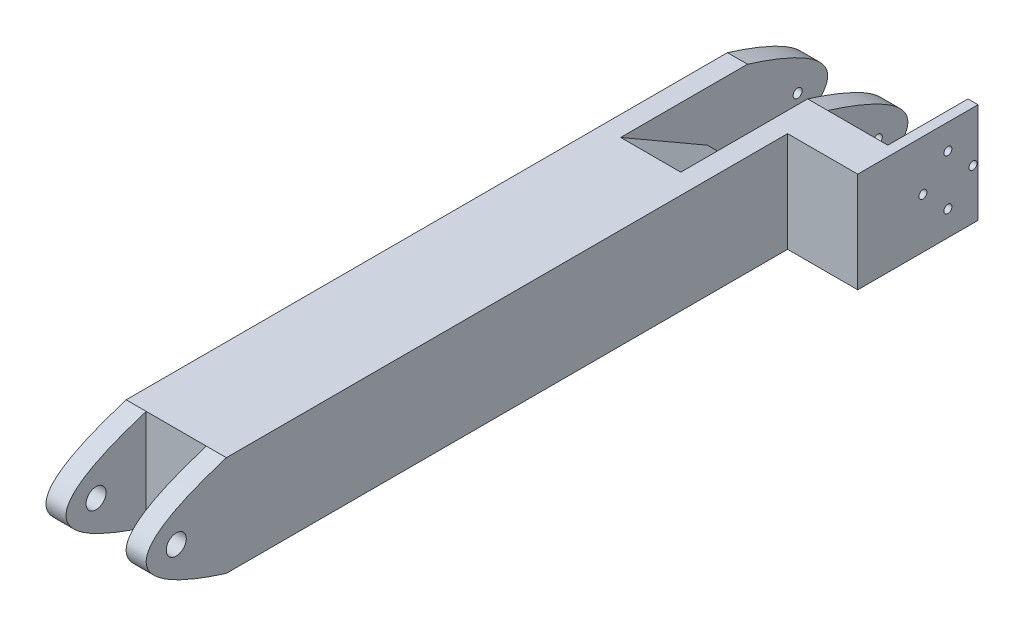
SolidWorks part; units mm, degrees
ref_plane "Front Plane" through (0, 0, 0) normal (0, 0, 1) x (1, 0, 0)
ref_plane "Top Plane" through (0, 0, 0) normal (0, 1, 0) x (1, 0, 0)
ref_plane "Right Plane" through (0, 0, 0) normal (1, 0, 0) x (0, 0, -1)
sketch "Sketch1" plane through (0, 0, 0) normal (1, 0, 0) x (0, 0, -1)
  line L0 (-255.8715, 42.046) -> (44.1285, 42.046)
  line L3 (-255.8715, -7.954) -> (44.1285, -7.954)
  circle A0 centre (-280.8715, 17.046) radius 5
  circle A1 centre (69.1285, 17.046) radius 2.25
  spline S0 degree 2 poles (44.1285, 42.046) (124.1285, 17.046) (44.1285, -7.954) knots 0 0 0 1 1 1
  spline S1 degree 2 poles (-255.8715, 42.046) (-335.8715, 17.046) (-255.8715, -7.954) knots 0 0 0 1 1 1
  dimension "D6" = 40
  dimension "D8" = 10
  dimension "D9" = 15
  dimension "D10" = 4.5
  dimension "D1" = 300
  dimension "D2" = 50
  dimension "D3" = 25
  dimension "D4" = 40
  dimension "D5" = 15
  dimension "D7" = 0
extrude "Boss-Extrude1" add sketch "Sketch1" along normal blind 50
sketch "Sketch2" plane through (0, 0, 0) normal (0, 1, 0) x (1, 0, 0)
  line L0 (50, 84.1285) -> (0, 84.1285) construction
  line L1 (10, 84.1285) -> (40, 84.1285)
  line L2 (10, 84.1285) -> (10, 24.1285)
  line L3 (10, 24.1285) -> (40, 24.1285)
  line L4 (40, 84.1285) -> (40, 24.1285)
  line L6 (0, 84.1285) -> (0, 44.1285) construction
  dimension "D1" = 10
  dimension "D2" = 10
  dimension "D3" = 60
extrude "Cut-Extrude1" cut sketch "Sketch2" along normal blind 52 and the other way blind 35
sketch "Sketch3" plane through (0, -7.954, 0) normal (0, -1, 0) x (1, 0, 0)
  line L0 (50, 295.8715) -> (0, 295.8715) construction
  line L1 (10, 295.8715) -> (40, 295.8715)
  line L2 (10, 295.8715) -> (10, 255.8715)
  line L3 (10, 255.8715) -> (40, 255.8715)
  line L4 (40, 295.8715) -> (40, 255.8715)
  line L5 (50, 255.8715) -> (0, 255.8715) construction
  dimension "D1" = 10
  dimension "D2" = 10
extrude "Cut-Extrude2" cut sketch "Sketch3" against normal blind 52
sketch "Sketch4" plane through (0, 0, 0) normal (-1, 0, 0) x (0, 0, 1)
  line L1 (-44.1285, 42.046) -> (255.8715, 42.046) construction
  line L5 (-24.1285, 17.046) -> (-24.1285, 42.046)
  line L6 (-24.1285, 42.046) -> (19.1728, 42.046)
  line L7 (-24.1285, 17.046) -> (19.1728, 42.046)
  line L8 (-24.1285, -7.954) -> (-24.1285, 42.046) construction
  dimension "D1" = 25
  dimension "D2" = 60
  dimension "D3" = 0
extrude "Cut-Extrude3" cut sketch "Sketch4" against normal blind 30 from offset 10 offset against normal yes
sketch "Sketch5" plane through (0, 0, 0) normal (-1, 0, 0) x (0, 0, 1)
  line L0 (-24.1285, -7.954) -> (-24.1285, 17.046)
  line L1 (-24.1285, 17.046) -> (19.1728, -7.954)
  line L2 (255.8715, -7.954) -> (-44.1285, -7.954) construction
  line L3 (19.1728, -7.954) -> (-24.1285, -7.954)
  line L5 (-24.1285, -7.954) -> (-24.1285, 17.046) construction
  dimension "D1" = 25
  dimension "D2" = 60
  dimension "D3" = 0
extrude "Cut-Extrude4" cut sketch "Sketch5" against normal blind 30 from offset 10 offset against normal yes
sketch "Sketch6" plane through (0, 42.046, 0) normal (0, 1, 0) x (1, 0, 0)
  line L0 (50, 24.1285) -> (85, 24.1285)
  line L1 (50, 44.1285) -> (50, -255.8715) construction
  line L2 (85, 24.1285) -> (85, 84.1285)
  line L3 (85, 84.1285) -> (80, 84.1285)
  line L4 (80, 84.1285) -> (80, 44.1285)
  line L5 (80, 44.1285) -> (50, 44.1285)
  line L9 (50, 84.1285) -> (40, 84.1285) construction
  line L20 (40, 44.1285) -> (40, -19.1728)
  line L21 (40, -19.1728) -> (10, -19.1728)
  line L22 (10, -19.1728) -> (10, 44.1285)
  line L23 (10, 44.1285) -> (0, 44.1285)
  line L24 (0, 44.1285) -> (0, -255.8715)
  line L25 (0, -255.8715) -> (10, -255.8715)
  line L26 (10, -255.8715) -> (40, -255.8715)
  line L27 (40, -255.8715) -> (50, -255.8715)
  line L28 (50, -255.8715) -> (50, 44.1285)
  line L29 (50, 44.1285) -> (40, 44.1285)
  line L38 (50, 24.1285) -> (50, 44.1285)
  point P10 (0, 0)
  dimension "D1" = 30
  dimension "D2" = 5
  dimension "D3" = 40
  dimension "D4" = 20
  dimension "D5" = 0
extrude "Boss-Extrude2" add sketch "Sketch6" against normal blind 50
sketch "Sketch7" plane through (85, 0, 0) normal (1, 0, 0) x (0, 0, -1)
  line L1 (24.1285, 42.046) -> (84.1285, 42.046) construction
  circle A0 centre (69.1285, 17.046) radius 15
  circle A1 centre (69.1285, 17.046) radius 2.25 construction
  point P2 (0, 0)
  point P3 (0, 0)
  point P8 (0, 0)
  dimension "D1" = 30
  dimension "D2" = 25
  dimension "D3" = 0
sketch "Sketch8" plane through (85, 0, 0) normal (1, 0, 0) x (0, 0, -1)
  circle A0 centre (69.1285, 29.546) radius 2
  circle A1 centre (69.1285, 17.046) radius 15 construction
  circle A2 centre (81.6285, 17.046) radius 2
  circle A3 centre (69.1285, 4.546) radius 2
  circle A4 centre (56.6285, 17.046) radius 2
  point P5 (0, 0)
  point P6 (0, 0)
  point P15 (0, 0)
  dimension "D2" = 4
  dimension "D1" = 12.5
  dimension "D3" = 12.5
  dimension "D4" = 12.5
  dimension "D5" = 12.5
extrude "Cut-Extrude5" cut sketch "Sketch8" against normal blind 10
